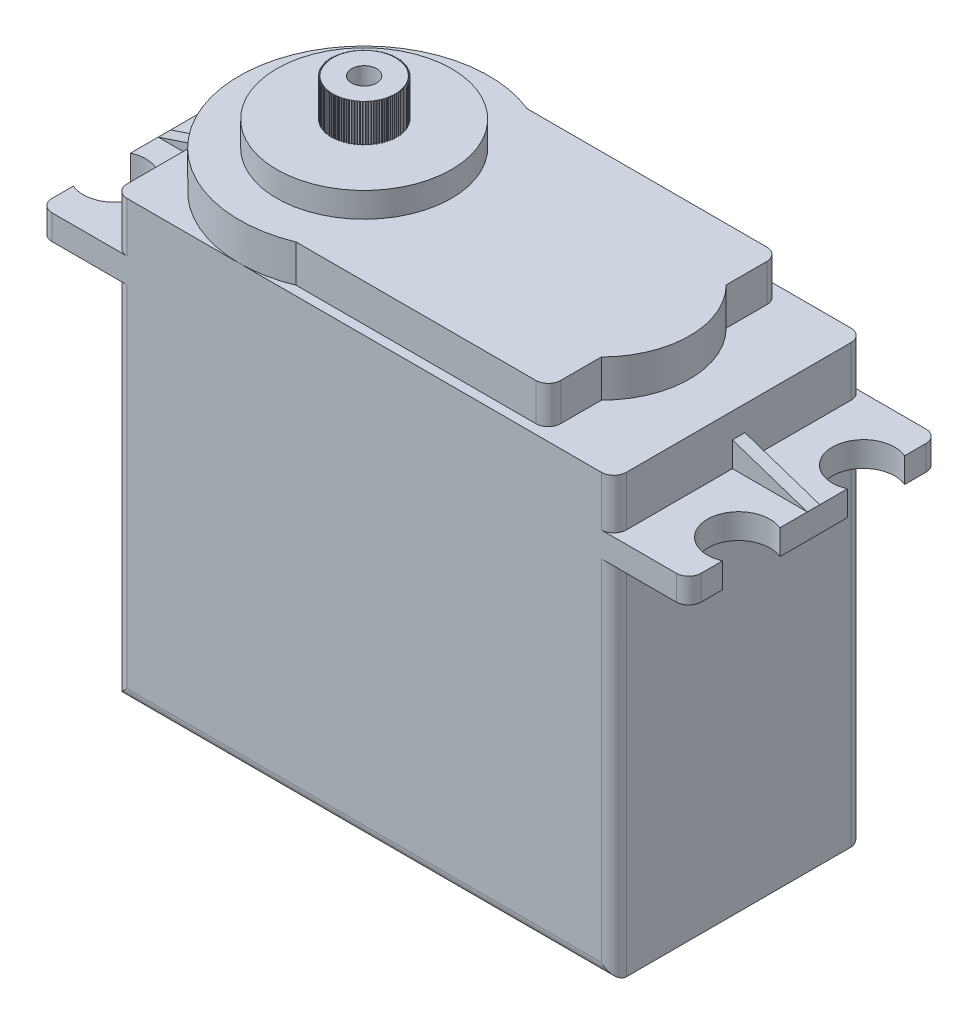
SolidWorks part; units mm, degrees
ref_plane "Front" through (0, 0, 0) normal (0, 0, 1) x (1, 0, 0)
ref_plane "Top" through (0, 0, 0) normal (0, 1, 0) x (1, 0, 0)
ref_plane "Right" through (0, 0, 0) normal (1, 0, 0) x (0, 0, -1)
sketch "Sketch1" plane through (0, 0, 0) normal (0, 1, 0) x (1, 0, 0)
  line L1 (0, 0) -> (40, 0)
  line L2 (0, 0) -> (0, 20)
  line L3 (0, 20) -> (40, 20)
  line L4 (40, 0) -> (40, 20)
extrude "Boss-Extrude1" add sketch "Sketch1" along normal blind 35
sketch "Sketch2" plane through (40, 0, 0) normal (1, 0, 0) x (0, 0, -1)
  line L0 (0, 29) -> (0, 31)
  line L2 (0, 31) -> (20, 31)
  line L3 (0, 35) -> (0, 0) construction
  line L4 (20, 35) -> (20, 0) construction
  line L5 (20, 31) -> (20, 29)
  line L6 (20, 29) -> (0, 29)
extrude "Boss-Extrude2" add sketch "Sketch2" along normal blind 6 and the other way blind 46
sketch "Sketch4" plane through (0, 31, 0) normal (0, 1, 0) x (1, 0, 0)
  circle A0 centre (45, 15) radius 2.5
  circle A1 centre (45, 5) radius 2.5
  circle A2 centre (-5, 5) radius 2.5
  circle A3 centre (-5, 15) radius 2.5
extrude "Cut-Extrude1" cut sketch "Sketch4" against normal through all
sketch "Sketch5" plane through (0, 31, 0) normal (0, 1, 0) x (1, 0, 0)
  line L0 (46, 9.5) -> (46, 10.5)
  line L1 (-6, 12.7087) -> (-6, 7.2913) construction
  line L2 (46, 12.7087) -> (46, 7.2913) construction
  line L3 (0, 20) -> (0, 0) construction
  line L4 (46, 10.5) -> (40, 10.5)
  line L5 (40, 0) -> (40, 20) construction
  line L6 (40, 10.5) -> (40, 9.5)
  line L7 (40, 9.5) -> (46, 9.5)
  line L9 (0, 9.5) -> (-6, 9.5)
  line L10 (0, 10.5) -> (0, 9.5)
  line L11 (-6, 10.5) -> (0, 10.5)
  line L12 (-6, 9.5) -> (-6, 10.5)
extrude "Boss-Extrude3" add sketch "Sketch5" along normal blind 2
sketch "Sketch6" plane through (0, 0, -9.5) normal (0, 0, 1) x (1, 0, 0)
  line L0 (40, 33) -> (46, 31)
  line L1 (-6, 31) -> (0, 33)
  line L2 (0, 35) -> (0, 31) construction
  line L3 (40, 33) -> (46, 33)
  line L4 (46, 33) -> (46, 31)
  line L5 (0, 33) -> (-6, 33)
  line L6 (-6, 33) -> (-6, 31)
extrude "Cut-Extrude2" cut sketch "Sketch6" against normal through all
sketch "Sketch8" plane through (0, 35, 0) normal (0, 1, 0) x (1, 0, 0)
  line L0 (34, 15) -> (34, 19.25)
  line L2 (34, 0.75) -> (13.7997, 0.75)
  line L4 (34, 0.75) -> (34, 5)
  line L6 (34, 19.25) -> (13.7997, 19.25)
  arc A0 (13.7997, 19.25) -> (13.7997, 0.75) centre (10, 10) ccw
  arc A1 (34, 15) -> (34, 5) centre (29, 10) cw
extrude "Boss-Extrude4" add sketch "Sketch8" along normal blind 3
sketch "Sketch9" plane through (0, 38, 0) normal (0, 1, 0) x (1, 0, 0)
  circle A0 centre (10, 10) radius 7
extrude "Boss-Extrude5" add sketch "Sketch9" along normal blind 2
sketch "Sketch10" plane through (0, 40, 0) normal (0, 1, 0) x (1, 0, 0)
  circle A0 centre (10, 10) radius 2.5
extrude "Boss-Extrude6" add sketch "Sketch10" along normal blind 3
sketch "Sketch11" plane through (0, 43, 0) normal (0, 1, 0) x (1, 0, 0)
  line L1 (10, 12.6) -> (10.0147, 12.5)
  line L2 (10, 12.6) -> (9.9853, 12.5)
  circle A1 centre (10, 10) radius 2.5 construction
  arc A2 (10.0147, 12.5) -> (9.9853, 12.5) centre (10, 10) ccw
extrude "Boss-Extrude7" add sketch "Sketch11" against normal up to surface (3 mm away) up to face at (10, 40, -3)
pattern_circular "CirPattern2" count 100 over 360 about axis through (10, 43, -10) along (0, -1, 0) of "Boss-Extrude7"
sketch "Sketch12" plane through (0, 43, 0) normal (0, 1, 0) x (1, 0, 0)
  circle A0 centre (10, 10) radius 1
extrude "Cut-Extrude3" cut sketch "Sketch12" against normal up to surface (8 mm away) up to face at (2.643, 35, -2.643)
fillet "Fillet1" radius 1 16 edges at (20, 0, -20) (20, 0, 0) (0, 33, 0) (34, 36.5, -19.25) (34, 36.5, -0.75) (40, 14.5, -20) (46, 30, -20) (40, 33, -20) (0, 14.5, -20) (-6, 30, -20) (0, 33, -20) (46, 30, 0) (40, 33, 0) (40, 14.5, 0) (-6, 30, 0) (0, 14.5, 0)
